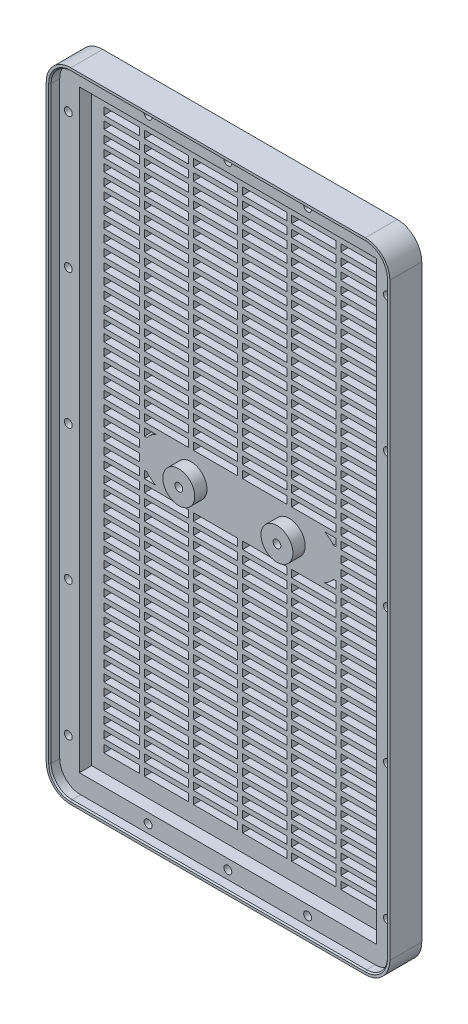
SolidWorks part; units mm, degrees
ref_plane "Front Plane" through (0, 0, 0) normal (0, 0, 1) x (1, 0, 0)
ref_plane "Top Plane" through (0, 0, 0) normal (0, 1, 0) x (1, 0, 0)
ref_plane "Right Plane" through (0, 0, 0) normal (1, 0, 0) x (0, 0, -1)
sketch "Sketch1" plane through (0, 0, 0) normal (0, 0, 1) x (1, 0, 0)
  line L1 (-70, -130) -> (70, -130)
  line L2 (-70, -130) -> (-70, 130)
  line L3 (-70, 130) -> (70, 130)
  line L4 (70, -130) -> (70, 130)
  line L5 (0, 130) -> (0, -130) construction
  line L6 (-70, 0) -> (70, 0) construction
  point P0 (0, 0)
  dimension "D1" = 140
  dimension "D2" = 260
extrude "Boss-Extrude1" add sketch "Sketch1" along normal blind 9
fillet "Fillet2" radius 10 4 edges at (-70, -130, 4.5) (70, -130, 4.5) (70, 130, 4.5) (-70, 130, 4.5)
sketch "Sketch3" plane through (0, 0, 9) normal (0, 0, 1) x (1, 0, 0)
  line L0 (60, 130) -> (-60, 130) construction
  line L1 (60.5, 121) -> (-60.5, 121)
  line L2 (60.5, 121) -> (60.5, -121)
  line L3 (60.5, -121) -> (-60.5, -121)
  line L4 (-60.5, 121) -> (-60.5, -121)
  line L5 (0, -121) -> (0, 121) construction
  line L6 (60.5, 0) -> (-60.5, 0) construction
  line L7 (-70, 120) -> (-70, -120) construction
  point P0 (0, 0)
  dimension "D1" = 9
  dimension "D2" = 9.5
extrude "Cut-Extrude1" cut sketch "Sketch3" against normal offset from surface (5 mm away) 4 up to face at (0, 0, 0)
sketch "Sketch7" plane through (0, 0, 4) normal (0, 0, 1) x (1, 0, 0)
  line L0 (0, 0) -> (-20, 0) construction
  line L1 (0, 0) -> (0, 45.0599) construction
  circle A0 centre (-20, 0) radius 6.5
  circle A1 centre (20, 0) radius 6.5
  dimension "D1" = 13
  dimension "D2" = 20
extrude "Boss-Extrude2" add sketch "Sketch7" along normal up to surface (5 mm away) up to face at (0, 0, 9)
hole_wizard "CBORE for M3 SHCS1" positions "Sketch4" profile "Sketch5" counterbore size "M3" standard "ANSI Metric" end condition through all
sketch "Sketch4" plane through (0, 0, 0) normal (0, 0, -1) x (-1, 0, 0)
  line L0 (65, -125) -> (-65, -125) construction
  line L1 (65, -125) -> (65, 125) construction
  line L2 (65, 125) -> (-65, 125) construction
  line L3 (-65, -125) -> (-65, 125) construction
  line L4 (0, 125) -> (0, -125) construction
  line L5 (65, 0) -> (-65, 0) construction
  circle A0 centre (0, 125) radius 2.2
  circle A1 centre (32.5, 125) radius 2.2
  circle A2 centre (-32.5, 125) radius 2.2
  circle A3 centre (-32.5, -125) radius 2.2
  circle A4 centre (0, -125) radius 2.2
  circle A5 centre (32.5, -125) radius 2.2
  circle A6 centre (-65, 0) radius 2.2
  circle A7 centre (-65, 55) radius 2.2
  circle A8 centre (-65, 110) radius 2.2
  circle A9 centre (-65, -110) radius 2.2
  circle A10 centre (-65, -55) radius 2.2
  circle A11 centre (65, 110) radius 2.2
  circle A12 centre (65, 55) radius 2.2
  circle A13 centre (65, 0) radius 2.2
  circle A14 centre (65, -110) radius 2.2
  circle A15 centre (65, -55) radius 2.2
  circle A16 centre (-20, 0) radius 2.2
  circle A17 centre (20, 0) radius 2.2
  point P57 (-32.5, 125)
  point P60 (0, 125)
  point P63 (32.5, 125)
  point P66 (65, 110)
  point P69 (65, 55)
  point P72 (65, 0)
  point P75 (65, -55)
  point P78 (65, -110)
  point P81 (32.5, -125)
  point P84 (0, -125)
  point P87 (-32.5, -125)
  point P90 (-65, -110)
  point P93 (-65, -55)
  point P96 (-65, 0)
  point P99 (-65, 55)
  point P102 (-65, 110)
  point P105 (-20, 0)
  point P108 (20, 0)
  dimension "D6" = 4.4
  dimension "D7" = 20
  dimension "D1" = 130
  dimension "D2" = 250
  dimension "D3" = 55
  dimension "D4" = 32.5
  dimension "D5" = 55
sketch "Sketch5" plane through (-20, 0, 0) normal (1, 0, 0) x (0, 1, 0)
  line L0 (0, 0) -> (0, 9)
  line L1 (0, 9) -> (1.6, 9)
  line L3 (1.6, 9) -> (1.6, 3)
  line L4 (1.6, 3) -> (3.25, 3)
  line L5 (3.25, 3) -> (3.25, 0)
  line L7 (3.25, 0) -> (0, 0)
  line L11 (0, -6.35) -> (0, 107.95) construction
  dimension "Thru Hole Dia." = 3.2
  dimension "Thru Hole Depth" = 9
  dimension "C'Bore Dia." = 6.5
  dimension "C'Bore Depth" = 3
sketch "Sketch8" plane through (0, 0, 0) normal (0, 0, -1) x (-1, 0, 0)
  line L0 (30, 0) -> (-30, 0) construction
  line L1 (-55.5, -116) -> (55.5, -116)
  line L2 (-55.5, -116) -> (-55.5, 116)
  line L3 (-55.5, 116) -> (55.5, 116)
  line L4 (55.5, -116) -> (55.5, 116)
  line L5 (0, 116) -> (0, -116) construction
  line L6 (-55.5, 0) -> (55.5, 0) construction
  line L7 (30, -10) -> (-30, -10)
  line L8 (30, 10) -> (-30, 10)
  arc A0 (30, -10) -> (30, 10) centre (30, 0) ccw
  arc A1 (-30, 10) -> (-30, -10) centre (-30, 0) ccw
  point P0 (0, 0)
  point P6 (0, 0)
  dimension "D3" = 10
  dimension "D1" = 111
  dimension "D2" = 232
  dimension "D4" = 60
extrude "Cut-Extrude2" cut sketch "Sketch8" against normal up to surface (4 mm away) up to face at (13.5, 0, 4)
sketch "Sketch9" plane through (0, 0, 0) normal (0, 0, -1) x (-1, 0, 0)
  line L0 (55.5, -116) -> (55.5, 116) construction
  line L1 (-55.5, 1) -> (55.5, 1) construction
  line L2 (-55.5, 1) -> (-55.5, -1) construction
  line L3 (-55.5, -1) -> (55.5, -1) construction
  line L4 (55.5, 1) -> (55.5, -1) construction
  line L5 (0, -1) -> (0, 1) construction
  line L6 (-55.5, 0) -> (55.5, 0) construction
  line L7 (-55.5, 6) -> (-55.5, 4)
  line L8 (-55.5, 6) -> (55.5, 6)
  line L9 (55.5, 6) -> (55.5, 4)
  line L10 (-55.5, 4) -> (55.5, 4)
  line L11 (-55.5, 11) -> (-55.5, 9)
  line L12 (-55.5, 11) -> (55.5, 11)
  line L13 (55.5, 11) -> (55.5, 9)
  line L14 (-55.5, 9) -> (55.5, 9)
  line L15 (-55.5, 16) -> (-55.5, 14)
  line L16 (-55.5, 16) -> (55.5, 16)
  line L17 (55.5, 16) -> (55.5, 14)
  line L18 (-55.5, 14) -> (55.5, 14)
  line L19 (-55.5, 21) -> (-55.5, 19)
  line L20 (-55.5, 21) -> (55.5, 21)
  line L21 (55.5, 21) -> (55.5, 19)
  line L22 (-55.5, 19) -> (55.5, 19)
  line L23 (-55.5, 26) -> (-55.5, 24)
  line L24 (-55.5, 26) -> (55.5, 26)
  line L25 (55.5, 26) -> (55.5, 24)
  line L26 (-55.5, 24) -> (55.5, 24)
  line L27 (-55.5, 31) -> (-55.5, 29)
  line L28 (-55.5, 31) -> (55.5, 31)
  line L29 (55.5, 31) -> (55.5, 29)
  line L30 (-55.5, 29) -> (55.5, 29)
  line L31 (-55.5, 36) -> (-55.5, 34)
  line L32 (-55.5, 36) -> (55.5, 36)
  line L33 (55.5, 36) -> (55.5, 34)
  line L34 (-55.5, 34) -> (55.5, 34)
  line L35 (-55.5, 41) -> (-55.5, 39)
  line L36 (-55.5, 41) -> (55.5, 41)
  line L37 (55.5, 41) -> (55.5, 39)
  line L38 (-55.5, 39) -> (55.5, 39)
  line L39 (-55.5, 46) -> (-55.5, 44)
  line L40 (-55.5, 46) -> (55.5, 46)
  line L41 (55.5, 46) -> (55.5, 44)
  line L42 (-55.5, 44) -> (55.5, 44)
  line L43 (-55.5, 51) -> (-55.5, 49)
  line L44 (-55.5, 51) -> (55.5, 51)
  line L45 (55.5, 51) -> (55.5, 49)
  line L46 (-55.5, 49) -> (55.5, 49)
  line L47 (-55.5, 56) -> (-55.5, 54)
  line L48 (-55.5, 56) -> (55.5, 56)
  line L49 (55.5, 56) -> (55.5, 54)
  line L50 (-55.5, 54) -> (55.5, 54)
  line L51 (-55.5, 61) -> (-55.5, 59)
  line L52 (-55.5, 61) -> (55.5, 61)
  line L53 (55.5, 61) -> (55.5, 59)
  line L54 (-55.5, 59) -> (55.5, 59)
  line L55 (-55.5, 66) -> (-55.5, 64)
  line L56 (-55.5, 66) -> (55.5, 66)
  line L57 (55.5, 66) -> (55.5, 64)
  line L58 (-55.5, 64) -> (55.5, 64)
  line L59 (-55.5, 71) -> (-55.5, 69)
  line L60 (-55.5, 71) -> (55.5, 71)
  line L61 (55.5, 71) -> (55.5, 69)
  line L62 (-55.5, 69) -> (55.5, 69)
  line L63 (-55.5, 76) -> (-55.5, 74)
  line L64 (-55.5, 76) -> (55.5, 76)
  line L65 (55.5, 76) -> (55.5, 74)
  line L66 (-55.5, 74) -> (55.5, 74)
  line L67 (-55.5, 81) -> (-55.5, 79)
  line L68 (-55.5, 81) -> (55.5, 81)
  line L69 (55.5, 81) -> (55.5, 79)
  line L70 (-55.5, 79) -> (55.5, 79)
  line L71 (-55.5, 86) -> (-55.5, 84)
  line L72 (-55.5, 86) -> (55.5, 86)
  line L73 (55.5, 86) -> (55.5, 84)
  line L74 (-55.5, 84) -> (55.5, 84)
  line L75 (-55.5, 91) -> (-55.5, 89)
  line L76 (-55.5, 91) -> (55.5, 91)
  line L77 (55.5, 91) -> (55.5, 89)
  line L78 (-55.5, 89) -> (55.5, 89)
  line L79 (-55.5, 96) -> (-55.5, 94)
  line L80 (-55.5, 96) -> (55.5, 96)
  line L81 (55.5, 96) -> (55.5, 94)
  line L82 (-55.5, 94) -> (55.5, 94)
  line L83 (-55.5, 101) -> (-55.5, 99)
  line L84 (-55.5, 101) -> (55.5, 101)
  line L85 (55.5, 101) -> (55.5, 99)
  line L86 (-55.5, 99) -> (55.5, 99)
  line L87 (-55.5, 106) -> (-55.5, 104)
  line L88 (-55.5, 106) -> (55.5, 106)
  line L89 (55.5, 106) -> (55.5, 104)
  line L90 (-55.5, 104) -> (55.5, 104)
  line L91 (-55.5, 111) -> (-55.5, 109)
  line L92 (-55.5, 111) -> (55.5, 111)
  line L93 (55.5, 111) -> (55.5, 109)
  line L94 (-55.5, 109) -> (55.5, 109)
  line L95 (-55.5, 116) -> (-55.5, 114)
  line L96 (-55.5, 116) -> (55.5, 116)
  line L97 (55.5, 116) -> (55.5, 114)
  line L98 (-55.5, 114) -> (55.5, 114)
  line L99 (-55.5, -4) -> (-55.5, -6)
  line L100 (-55.5, -4) -> (55.5, -4)
  line L101 (55.5, -4) -> (55.5, -6)
  line L102 (-55.5, -6) -> (55.5, -6)
  line L103 (-55.5, -9) -> (-55.5, -11)
  line L104 (-55.5, -9) -> (55.5, -9)
  line L105 (55.5, -9) -> (55.5, -11)
  line L106 (-55.5, -11) -> (55.5, -11)
  line L107 (-55.5, -14) -> (-55.5, -16)
  line L108 (-55.5, -14) -> (55.5, -14)
  line L109 (55.5, -14) -> (55.5, -16)
  line L110 (-55.5, -16) -> (55.5, -16)
  line L111 (-55.5, -19) -> (-55.5, -21)
  line L112 (-55.5, -19) -> (55.5, -19)
  line L113 (55.5, -19) -> (55.5, -21)
  line L114 (-55.5, -21) -> (55.5, -21)
  line L115 (-55.5, -24) -> (-55.5, -26)
  line L116 (-55.5, -24) -> (55.5, -24)
  line L117 (55.5, -24) -> (55.5, -26)
  line L118 (-55.5, -26) -> (55.5, -26)
  line L119 (-55.5, -29) -> (-55.5, -31)
  line L120 (-55.5, -29) -> (55.5, -29)
  line L121 (55.5, -29) -> (55.5, -31)
  line L122 (-55.5, -31) -> (55.5, -31)
  line L123 (-55.5, -34) -> (-55.5, -36)
  line L124 (-55.5, -34) -> (55.5, -34)
  line L125 (55.5, -34) -> (55.5, -36)
  line L126 (-55.5, -36) -> (55.5, -36)
  line L127 (-55.5, -39) -> (-55.5, -41)
  line L128 (-55.5, -39) -> (55.5, -39)
  line L129 (55.5, -39) -> (55.5, -41)
  line L130 (-55.5, -41) -> (55.5, -41)
  line L131 (-55.5, -44) -> (-55.5, -46)
  line L132 (-55.5, -44) -> (55.5, -44)
  line L133 (55.5, -44) -> (55.5, -46)
  line L134 (-55.5, -46) -> (55.5, -46)
  line L135 (-55.5, -49) -> (-55.5, -51)
  line L136 (-55.5, -49) -> (55.5, -49)
  line L137 (55.5, -49) -> (55.5, -51)
  line L138 (-55.5, -51) -> (55.5, -51)
  line L139 (-55.5, -54) -> (-55.5, -56)
  line L140 (-55.5, -54) -> (55.5, -54)
  line L141 (55.5, -54) -> (55.5, -56)
  line L142 (-55.5, -56) -> (55.5, -56)
  line L143 (-55.5, -59) -> (-55.5, -61)
  line L144 (-55.5, -59) -> (55.5, -59)
  line L145 (55.5, -59) -> (55.5, -61)
  line L146 (-55.5, -61) -> (55.5, -61)
  line L147 (-55.5, -64) -> (-55.5, -66)
  line L148 (-55.5, -64) -> (55.5, -64)
  line L149 (55.5, -64) -> (55.5, -66)
  line L150 (-55.5, -66) -> (55.5, -66)
  line L151 (-55.5, -69) -> (-55.5, -71)
  line L152 (-55.5, -69) -> (55.5, -69)
  line L153 (55.5, -69) -> (55.5, -71)
  line L154 (-55.5, -71) -> (55.5, -71)
  line L155 (-55.5, -74) -> (-55.5, -76)
  line L156 (-55.5, -74) -> (55.5, -74)
  line L157 (55.5, -74) -> (55.5, -76)
  line L158 (-55.5, -76) -> (55.5, -76)
  line L159 (-55.5, -79) -> (-55.5, -81)
  line L160 (-55.5, -79) -> (55.5, -79)
  line L161 (55.5, -79) -> (55.5, -81)
  line L162 (-55.5, -81) -> (55.5, -81)
  line L163 (-55.5, -84) -> (-55.5, -86)
  line L164 (-55.5, -84) -> (55.5, -84)
  line L165 (55.5, -84) -> (55.5, -86)
  line L166 (-55.5, -86) -> (55.5, -86)
  line L167 (-55.5, -89) -> (-55.5, -91)
  line L168 (-55.5, -89) -> (55.5, -89)
  line L169 (55.5, -89) -> (55.5, -91)
  line L170 (-55.5, -91) -> (55.5, -91)
  line L171 (-55.5, -94) -> (-55.5, -96)
  line L172 (-55.5, -94) -> (55.5, -94)
  line L173 (55.5, -94) -> (55.5, -96)
  line L174 (-55.5, -96) -> (55.5, -96)
  line L175 (-55.5, -99) -> (-55.5, -101)
  line L176 (-55.5, -99) -> (55.5, -99)
  line L177 (55.5, -99) -> (55.5, -101)
  line L178 (-55.5, -101) -> (55.5, -101)
  line L179 (-55.5, -104) -> (-55.5, -106)
  line L180 (-55.5, -104) -> (55.5, -104)
  line L181 (55.5, -104) -> (55.5, -106)
  line L182 (-55.5, -106) -> (55.5, -106)
  line L183 (-55.5, -109) -> (-55.5, -111)
  line L184 (-55.5, -109) -> (55.5, -109)
  line L185 (55.5, -109) -> (55.5, -111)
  line L186 (-55.5, -111) -> (55.5, -111)
  line L187 (-55.5, -114) -> (-55.5, -116)
  line L188 (-55.5, -114) -> (55.5, -114)
  line L189 (55.5, -114) -> (55.5, -116)
  line L190 (-55.5, -116) -> (55.5, -116)
  line L192 (-55.5, 1) -> (-27.0207, 1)
  line L193 (-55.5, 1) -> (-55.5, -1)
  line L194 (-55.5, -1) -> (-27.0207, -1)
  line L195 (-27.0207, 1) -> (-27.0207, -1)
  line L196 (-41.2604, -1) -> (-41.2604, 1) construction
  line L197 (-55.5, 0) -> (-27.0207, 0) construction
  line L198 (55.5, 1) -> (34.8738, 1)
  line L199 (55.5, 1) -> (55.5, -1)
  line L200 (55.5, -1) -> (34.8738, -1)
  line L201 (34.8738, 1) -> (34.8738, -1)
  line L202 (45.1869, -1) -> (45.1869, 1) construction
  line L203 (55.5, 0) -> (34.8738, 0) construction
  point P0 (0, 0)
  point P378 (-41.2604, 0)
  point P481 (45.1869, 0)
  dimension "D1" = 2
  dimension "D2" = 24
  dimension "D3" = 24
extrude "Boss-Extrude3" add sketch "Sketch9" against normal up to surface (4 mm away) up to face at (0, 0, 4)
sketch "Sketch10" plane through (0, 0, 0) normal (0, 0, -1) x (-1, 0, 0)
  line L0 (-55.5, 114) -> (55.5, 114) construction
  line L1 (-1, -114) -> (1, -114)
  line L2 (-1, -114) -> (-1, 114)
  line L3 (-1, 114) -> (1, 114)
  line L4 (1, -114) -> (1, 114)
  line L5 (0, 114) -> (0, -114) construction
  line L6 (-1, 0) -> (1, 0) construction
  line L7 (19, -114) -> (19, 114) construction
  line L8 (19, -114) -> (21, -114)
  line L9 (21, -114) -> (21, 114) construction
  line L10 (19, 114) -> (21, 114)
  line L11 (39, -114) -> (39, 114)
  line L12 (39, -114) -> (41, -114)
  line L13 (41, -114) -> (41, 114)
  line L14 (39, 114) -> (41, 114)
  line L15 (-21, -114) -> (-21, 114) construction
  line L16 (-21, -114) -> (-19, -114)
  line L17 (-19, -114) -> (-19, 114) construction
  line L18 (-21, 114) -> (-19, 114)
  line L19 (-41, -114) -> (-41, 114)
  line L20 (-41, -114) -> (-39, -114)
  line L21 (-39, -114) -> (-39, 114)
  line L22 (-41, 114) -> (-39, 114)
  line L23 (-21, 6.7097) -> (-19, 6.7097)
  line L24 (-21, -8.1301) -> (-19, -8.1301)
  line L25 (-21, 6.7097) -> (-21, 114)
  line L26 (-19, 114) -> (-19, 6.7097)
  line L27 (-19, -8.1301) -> (-19, -114)
  line L28 (-21, -114) -> (-21, -8.1301)
  line L29 (19, 7.8106) -> (21, 7.8106)
  line L30 (19, -6.9922) -> (21, -6.9922)
  line L31 (21, -6.9922) -> (21, -114)
  line L32 (19, -114) -> (19, -6.9922)
  line L33 (19, 7.8106) -> (19, 114)
  line L34 (21, 114) -> (21, 7.8106)
  point P0 (0, 0)
  point P27 (-21, 6.7097)
  point P28 (-21, -8.1301)
  point P29 (-19, -8.1301)
  point P30 (-19, 6.7097)
  dimension "D1" = 2
  dimension "D2" = 3
  dimension "D3" = 3
extrude "Boss-Extrude4" add sketch "Sketch10" against normal up to surface (4 mm away) up to face at (0, -112.5, 4)
ref_plane "Plane1" through (0, 82, 0) normal (0, 1, 0) x (1, 0, 0)
sketch "Sketch11" plane through (0, 82, 0) normal (0, 1, 0) x (1, 0, 0)
  line L0 (-66, 0) -> (-66, -5)
  line L1 (60, 0) -> (-60, 0) construction
  line L2 (-66, -5) -> (-62, -5)
  line L3 (-62, -5) -> (-60.5, -2.5)
  line L4 (-60.5, -2.5) -> (-62, 0)
  line L5 (-62, 0) -> (-66, 0)
  line L6 (-64, -5) -> (-64, 0) construction
  line L7 (-70, -9) -> (-70, 0) construction
  line L8 (0, 0) -> (0, 28.0861) construction
  line L9 (62, 0) -> (66, 0)
  line L10 (60.5, -2.5) -> (62, 0)
  line L11 (62, -5) -> (60.5, -2.5)
  line L12 (66, -5) -> (62, -5)
  line L13 (66, 0) -> (66, -5)
  dimension "D1" = 4
  dimension "D2" = 1.5
  dimension "D3" = 6
  dimension "D4" = 5
extrude "Cut-Extrude3" cut sketch "Sketch11" against normal mid plane 20
mirror "Mirror1" about plane through (0, 0, 0) normal (0, 1, 0) of "Cut-Extrude3"
sketch "Sketch12" plane through (0, 0, 9) normal (0, 0, 1) x (1, 0, 0)
  line L0 (-60, -130) -> (60, -130) construction
  line L1 (70, -120) -> (70, 120) construction
  line L2 (-70, 120) -> (-70, -120) construction
  line L3 (60, 130) -> (-60, 130) construction
  line L4 (-60, -130) -> (60, -130)
  line L5 (70, -120) -> (70, 120)
  line L6 (-70, 120) -> (-70, -120)
  line L7 (60, 130) -> (-60, 130)
  line L8 (-60, -128.5) -> (60, -128.5)
  line L9 (68.5, -120) -> (68.5, 120)
  line L10 (60, 128.5) -> (-60, 128.5)
  line L11 (-68.5, 120) -> (-68.5, -120)
  arc A0 (-70, -120) -> (-60, -130) centre (-60, -120) ccw construction
  arc A1 (60, -130) -> (70, -120) centre (60, -120) ccw construction
  arc A2 (70, 120) -> (60, 130) centre (60, 120) ccw construction
  arc A3 (-60, 130) -> (-70, 120) centre (-60, 120) ccw construction
  arc A4 (-70, -120) -> (-60, -130) centre (-60, -120) ccw
  arc A5 (60, -130) -> (70, -120) centre (60, -120) ccw
  arc A6 (70, 120) -> (60, 130) centre (60, 120) ccw
  arc A7 (-60, 130) -> (-70, 120) centre (-60, 120) ccw
  arc A8 (-68.5, -120) -> (-60, -128.5) centre (-60, -120) ccw
  arc A9 (60, -128.5) -> (68.5, -120) centre (60, -120) ccw
  arc A10 (68.5, 120) -> (60, 128.5) centre (60, 120) ccw
  arc A11 (-60, 128.5) -> (-68.5, 120) centre (-60, 120) ccw
  dimension "D1" = 1.5
extrude "Boss-Extrude5" add sketch "Sketch12" along normal blind 4
chamfer "Chamfer1" distance 0.5 angle 45 8 edges at (66.0104, -126.0104, 13) (68.5, 0, 13) (0, -128.5, 13) (66.0104, 126.0104, 13) (-66.0104, -126.0104, 13) (0, 128.5, 13) (-68.5, 0, 13) (-66.0104, 126.0104, 13)
